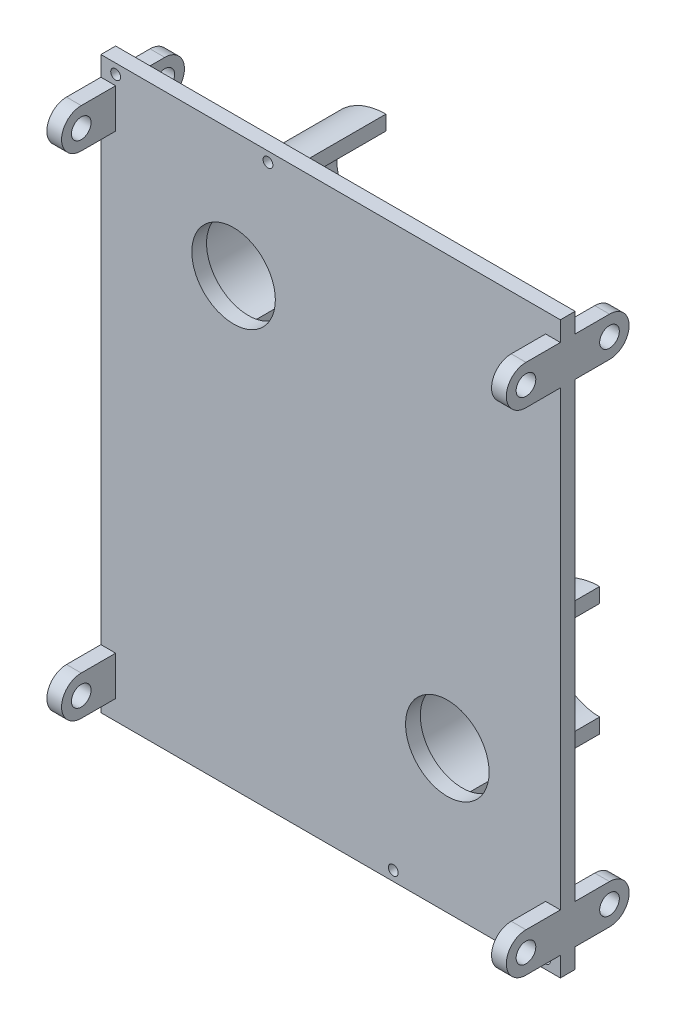
SolidWorks part; units mm, degrees
material "2024-T4"
ref_plane "Front Plane" through (0, 0, 0) normal (0, 0, 1) x (1, 0, 0)
ref_plane "Top Plane" through (0, 0, 0) normal (0, 1, 0) x (1, 0, 0)
ref_plane "Right Plane" through (0, 0, 0) normal (1, 0, 0) x (0, 0, -1)
sketch "Sketch1" plane through (0, 0, 0) normal (0, 0, 1) x (1, 0, 0)
  line L1 (-46.75, -58) -> (46.75, -58)
  line L2 (-46.75, -58) -> (-46.75, 58)
  line L3 (-46.75, 58) -> (46.75, 58)
  line L4 (46.75, -58) -> (46.75, 58)
  line L5 (-46.75, -58) -> (46.75, 58) construction
  line L6 (-46.75, 58) -> (46.75, -58) construction
  circle A0 centre (-22.8181, 25.0296) radius 20 construction
  circle A1 centre (24.0245, 19.8034) radius 20 construction
  point P0 (0, 0)
  dimension "D3" = 40
  dimension "D1" = 93.5
  dimension "D2" = 116
extrude "Boss-Extrude1" add sketch "Sketch1" along normal blind 3 contours L3 L4 L1 L2
sketch "Sketch2" plane through (0, 0, 3) normal (0, 0, 1) x (1, 0, 0)
  line L0 (-46.75, -58) -> (-46.75, 58) construction
  line L1 (-46.75, 58) -> (46.75, 58) construction
  line L2 (46.75, 0) -> (-46.75, 0) construction
  line L3 (46.75, -58) -> (46.75, 58) construction
  line L4 (-46.75, -58) -> (46.75, -58) construction
  circle A0 centre (-19.75, 32.5) radius 20 construction
  circle A1 centre (23.75, -29) radius 20 construction
  circle A2 centre (-19.75, 32.5) radius 8.5
  circle A3 centre (23.75, -29) radius 8.5
  dimension "D2" = 40
  dimension "D6" = 17
  dimension "D4" = 29
  dimension "D5" = 32.5
  dimension "D3" = 23
  dimension "D1" = 43.5
  dimension "D7" = 25.5
  dimension "D8" = 29
  dimension "D9" = 27
extrude "Cut-Extrude1" cut sketch "Sketch2" against normal through all
sketch "Sketch4" plane through (-46.75, 0, 0) normal (-1, 0, 0) x (0, 0, 1)
  line L0 (0, 0) -> (10.9251, 0) construction
  line L1 (0, 58) -> (0, 50) construction
  line L2 (0, -58) -> (0, 58) construction
  line L3 (0, 50) -> (-7, 50) construction
  line L4 (-7, 54) -> (0, 54)
  line L5 (0, 54) -> (0, 46)
  line L6 (0, 46) -> (-7, 46)
  line L7 (0, -50) -> (-7, -50) construction
  line L8 (0, -58) -> (0, -50) construction
  line L9 (0, -46) -> (-7, -46)
  line L10 (0, -54) -> (0, -46)
  line L11 (-7, -54) -> (0, -54)
  line L12 (1.5, -58) -> (1.5, -62.9921) construction
  line L13 (3, -58) -> (0, -58) construction
  line L14 (3, 46) -> (10, 46)
  line L15 (3, 54) -> (3, 46)
  line L16 (10, 54) -> (3, 54)
  line L17 (10, -54) -> (3, -54)
  line L18 (3, -54) -> (3, -46)
  line L19 (3, -46) -> (10, -46)
  circle A0 centre (-7, 50) radius 2
  arc A1 (-7, 54) -> (-7, 46) centre (-7, 50) ccw
  arc A2 (-7, -54) -> (-7, -46) centre (-7, -50) cw
  circle A3 centre (-7, -50) radius 2
  circle A4 centre (10, 50) radius 2
  arc A5 (10, 54) -> (10, 46) centre (10, 50) cw
  circle A6 centre (10, -50) radius 2
  arc A7 (10, -54) -> (10, -46) centre (10, -50) ccw
  dimension "D3" = 8
  dimension "D4" = 4
  dimension "D1" = 7
  dimension "D2" = 8
extrude "Boss-Extrude3" add sketch "Sketch4" against normal blind 3
sketch "Sketch6" plane through (0, 0, 3) normal (0, 0, 1) x (1, 0, 0)
  line L0 (-46.75, 58) -> (-46.75, 54) construction
  line L1 (-46.75, 56) -> (-43.75, 56) construction
  line L2 (-46.75, 58) -> (-9.75, 58) construction
  line L3 (46.75, -58) -> (46.75, -54) construction
  line L4 (46.75, -58) -> (46.75, 58) construction
  line L5 (46.75, -56) -> (43.75, -56) construction
  line L6 (43.75, -56) -> (12.75, -56) construction
  circle A0 centre (-43.75, 56) radius 1
  circle A1 centre (-12.75, 56) radius 1
  circle A2 centre (43.75, -56) radius 1
  circle A3 centre (12.75, -56) radius 1
  dimension "D2" = 2
  dimension "D6" = 2
  dimension "D10" = 2
  dimension "D11" = 2
  dimension "D1" = 4
  dimension "D3" = 3
  dimension "D4" = 37
  dimension "D5" = 3
  dimension "D7" = 3
  dimension "D8" = 4
  dimension "D9" = 31
extrude "Cut-Extrude2" cut sketch "Sketch6" against normal blind 10
sketch "Sketch5" plane through (0, 0, 0) normal (0, 0, -1) x (-1, 0, 0)
  line L0 (19.75, 32.5) -> (19.75, 45.5) construction
  line L5 (-23.75, -29) -> (-23.75, -16) construction
  line L10 (19.75, 32.5) -> (29.75, 32.5) construction
  line L15 (19.75, 42.5) -> (19.75, 45.5)
  line L16 (19.75, 22.5) -> (19.75, 19.5)
  line L17 (-23.75, -19) -> (-23.75, -16)
  line L18 (-23.75, -39) -> (-23.75, -42)
  arc A0 (19.75, 22.5) -> (19.75, 42.5) centre (19.75, 32.5) ccw
  arc A1 (19.75, 19.5) -> (19.75, 45.5) centre (19.75, 32.5) ccw
  arc A2 (-23.75, -39) -> (-23.75, -19) centre (-23.75, -29) ccw
  arc A3 (-23.75, -42) -> (-23.75, -16) centre (-23.75, -29) ccw
  point P9 (19.75, 42.5)
  point P20 (-23.75, -19)
  point P26 (32.75, 32.5)
  dimension "D1" = 20
  dimension "D2" = 3
  dimension "D4" = 3
  dimension "D5" = 20
extrude "Boss-Extrude4" add sketch "Sketch5" along normal blind 28 contours L16 A1 L15 A0 | A3 L17 A2 L18 region at (-20.0407, 44, 0)
mirror "Mirror1" about plane through (0, 0, 0) normal (1, 0, 0) of "Boss-Extrude3"
mirror "Mirror2" [suppressed] of bodies 107
delete or keep bodies "Body-Delete/Keep 1" [suppressed] type delete bodies bodies 107
equation "\"mini-flipper-shaft-diameter\"= 26mm"
equation "\"mini-shaft-ring-groove-diam\"= 7.8mm"
equation "\"mini-shaft-ring-groove-width\"= 1mm"
equation "\"dtCoverPlate-DistFrom-GearCent\"= 73mm"
equation "\"wormGearShaft-L\"= \"dtCoverPlate-DistFrom-GearCent\" - 27.75 + 3.75"
equation "\"wormGearShaft-Dsmall\"= 6mm"
equation "\"wormGearShaft-Dworm\"= 12mm"
equation "\"wormL-D\" = 12mm"
equation "\"wormR-D\" = 15mm"
equation "\"wormGearL-D\" = 46mm"
equation "\"wormGearR-D\" = 50mm"
equation "\"D5@Sketch2\"=\"wormGearR-D\"/2 + \"wormR-D\"/2"
equation "\"D4@Sketch2\"=\"wormGearL-D\"/2 + \"wormL-D\"/2"
